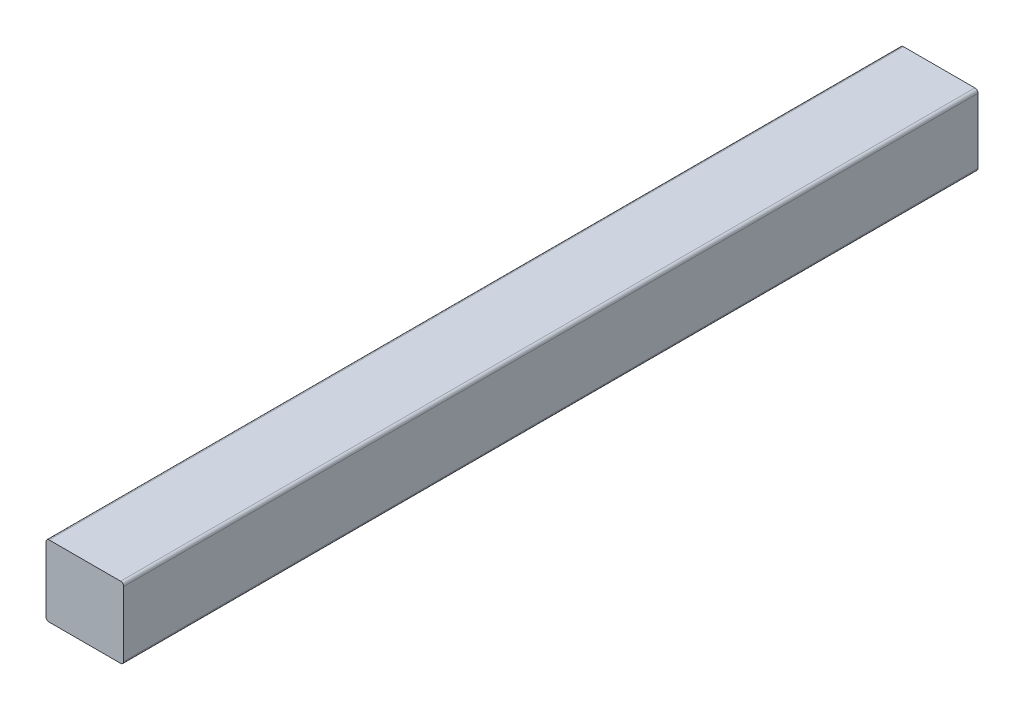
SolidWorks part; units mm, degrees
material "Plain Carbon Steel"
ref_plane "Front Plane" through (0, 0, 0) normal (0, 0, 1) x (1, 0, 0)
ref_plane "Top Plane" through (0, 0, 0) normal (0, 1, 0) x (1, 0, 0)
ref_plane "Right Plane" through (0, 0, 0) normal (1, 0, 0) x (0, 0, -1)
sketch "Sketch1" plane through (0, 0, 0) normal (0, 0, 1) x (1, 0, 0)
  line L0 (50, 2) -> (50, 0) construction
  line L1 (2, 0) -> (48, 0)
  line L2 (0, 2) -> (0, 43.8258)
  line L3 (2, 45.8258) -> (48, 45.8258)
  line L4 (50, 2) -> (50, 43.8258)
  line L5 (50, 0) -> (48, 0) construction
  line L6 (0, 2) -> (0, 0) construction
  line L7 (0, 0) -> (2, 0) construction
  line L9 (-250, 0) -> (50, 0) construction
  arc A0 (2, 0) -> (0, 2) centre (2, 2) cw
  arc A1 (48, 0) -> (50, 2) centre (48, 2) ccw
  arc A2 (48, 45.8258) -> (50, 43.8258) centre (48, 43.8258) cw
  arc A3 (0, 43.8258) -> (2, 45.8258) centre (2, 43.8258) cw
  point P7 (50, 0)
  point P12 (50, 45.8258)
  point P15 (0, 45.8258)
  point P16 (0, 0)
  dimension "D3" = 2
  dimension "D2" = 50
extrude "Boss-Extrude1" add sketch "Sketch1" along normal blind 550
sketch "Center_lines" plane through (0, 45.8258, 0) normal (0, 1, 0) x (1, 0, 0)
  line L0 (25, 28.7626) -> (25, -578.7626) construction
  line L1 (0, -275) -> (50, -275) construction
  line L2 (48, 0) -> (2, 0) construction
  line L3 (48, -550) -> (48, 0) construction
  line L4 (0, -550) -> (0, 0) construction
  point P6 (25, 0)
  point P7 (25, -275)
  point P10 (48, -275)
  point P15 (25, -275)
sketch "Tube_end_reference" plane through (0, 0, 550) normal (0, 0, 1) x (1, 0, 0)
  line L0 (50, 2) -> (50, 43.8258) construction
  line L1 (50, 45.8258) -> (0, 45.8258) construction
  line L2 (50, 45.8258) -> (50, 0) construction
  line L3 (50, 0) -> (0, 0) construction
  line L4 (0, 45.8258) -> (0, 0) construction
  line L5 (0, 43.8258) -> (0, 2) construction
  line L6 (0, 45.8258) -> (50, 45.8258) construction
  line L7 (2, 0) -> (48, 0) construction
sketch "Tube_corners_R" plane through (50, 0, 0) normal (1, 0, 0) x (0, 0, -1)
  line L0 (-550, 0) -> (0, 0) construction
  line L1 (-550, 45.8258) -> (0, 45.8258) construction
sketch "Tube_corners_L" plane through (0, 0, 0) normal (-1, 0, 0) x (0, 0, 1)
  line L0 (550, 45.8258) -> (0, 45.8258) construction
  line L1 (550, 0) -> (0, 0) construction
equation "\"Movement\"= 350"
equation "\"Block spacing\"= 200"
equation "\"Base length\"= \"Movement\" + \"Block spacing\""
equation "\"D1@Boss-Extrude1\"= \"Base length\""
